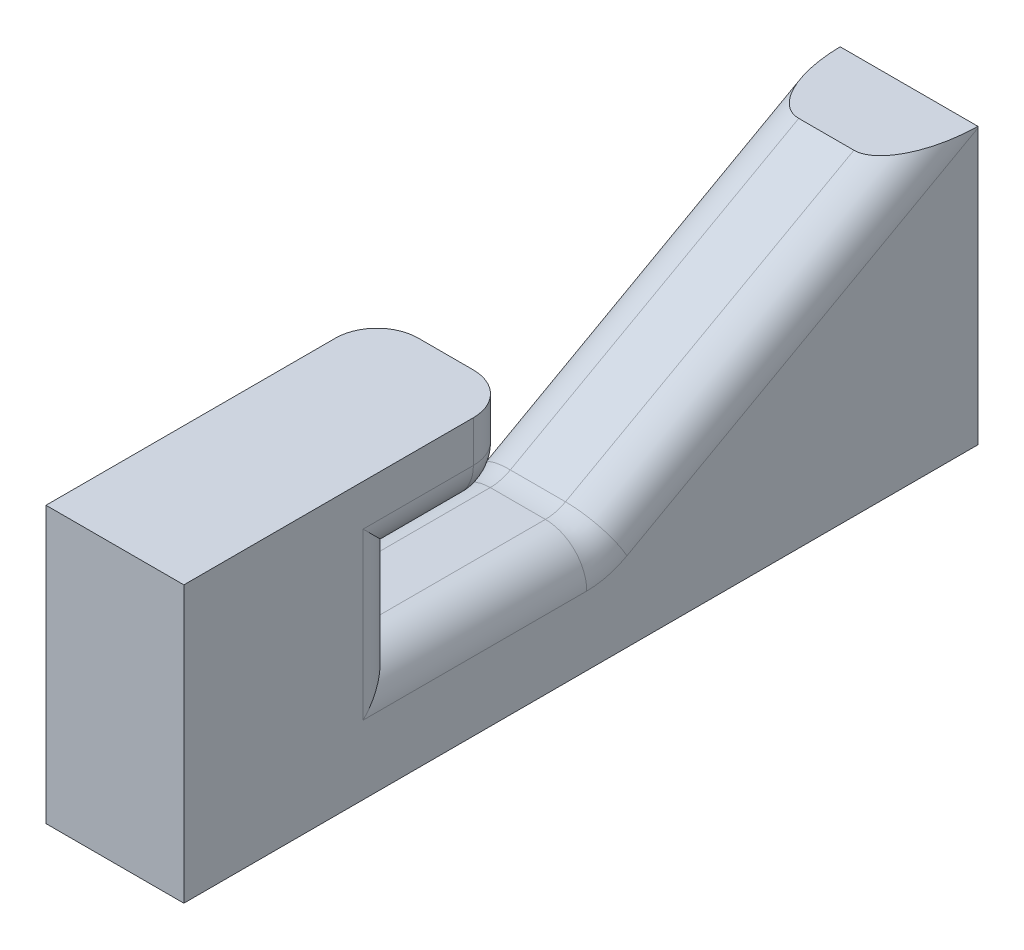
SolidWorks part; units mm, degrees
ref_plane "Front Plane" through (0, 0, 0) normal (1, 0, 0) x (0, 1, 0)
ref_plane "Top Plane" through (0, 0, 0) normal (0, 0, 1) x (0, 1, 0)
ref_plane "Right Plane" through (0, 0, 0) normal (0, 1, 0) x (-1, 0, 0)
sketch "Sketch2" plane through (0, 0, 0) normal (1, 0, 0) x (0, 1, 0)
  line L1 (0, 0) -> (10, 0)
  line L2 (0, 0) -> (0, 28.8)
  line L3 (0, 28.8) -> (10, 28.8)
  line L4 (10, 0) -> (10, 28.8)
  dimension "D1" = 28.8
  dimension "D2" = 10
extrude "Boss-Extrude1" add sketch "Sketch2" along normal blind 5
sketch "Sketch3" plane through (5, 0, 0) normal (1, 0, 0) x (0, 1, 0)
  line L0 (4, 16.8) -> (4, 13.8)
  line L1 (10, 28.8) -> (7, 28.8)
  line L2 (10, 28.8) -> (10, 16.8)
  line L3 (10, 16.8) -> (7, 16.8)
  line L4 (7, 28.8) -> (7, 16.8)
  line L5 (7, 16.8) -> (4, 16.8)
  line L6 (7, 16.8) -> (7, 20.8)
  line L7 (7, 20.8) -> (4, 20.8)
  line L8 (4, 16.8) -> (4, 20.8)
  line L10 (4, 13.8) -> (10, 3)
  line L11 (10, 0) -> (10, 28.8) construction
  line L12 (0, 0) -> (10, 0) construction
  line L13 (10, 3) -> (10, 16.8)
  line M12 (10, 0) -> (10, 28.8)
  dimension "D1" = 12
  dimension "D2" = 3
  dimension "D3" = 3
  dimension "D4" = 4
  dimension "D5" = 3
  dimension "D6" = 3
extrude "Cut-Extrude1" cut sketch "Sketch3" against normal through all contours L8 L5 L4 L7 | L0 L10 L3 L5 M12 region at (5, 7.6429, 12.0214) region at (5, 5.5, 18.8)
fillet "Fillet2" radius 1.5 12 edges at (2.5, 7, 16.8) (5, 7, 18.8) (5, 4, 17.3) (5, 5.5, 20.8) (0, 4, 17.3) (0, 5.5, 20.8) (0, 7, 18.8) (0, 7, 8.4) (5, 7, 8.4) (2.5, 4, 13.8) (0, 8.5, 16.8) (5, 8.5, 16.8)
equation "\"whitekey_cutout_length\"= 101.5"
equation "\"wall_thickness\"=10"
equation "\"base_mount_height\"=40"
equation "\"base_rear_length\"=80"
equation "\"D1@Sketch2\"=\"base_mount_height\"-11-0.2"
equation "\"key_mount_recess_length\"=50"
equation "\"key_mount_recess_height\"=12.5"
equation "\"key_mount_recess_depth\"=1.5"
equation "\"guide_brace_height\"=20"
equation "\"guide_brace_thickness\"=2"
equation "\"dowel_recess_depth\"=9"
equation "\"dowel_recess_offset\"=3"
equation "\"base_front_length\"=111.5"
equation "\"screw_hole_wall_offset\"=7.25"
equation "\"screw_hole_edge_inset\"=4.5"
equation "\"screw_hole_diameter\"=3.8"
equation "\"screw_head_hole_diameter\"=6.7"
equation "\"screw_nut_hole_side_len\"=3.5"
equation "\"screw_shaft_diameter\"=3.5"
equation "\"switch_board_width\"=30"
equation "\"heatset_insert_hole_diameter\"=4.8"
equation "\"heatset_insert_hole_depth\"=3.8"
